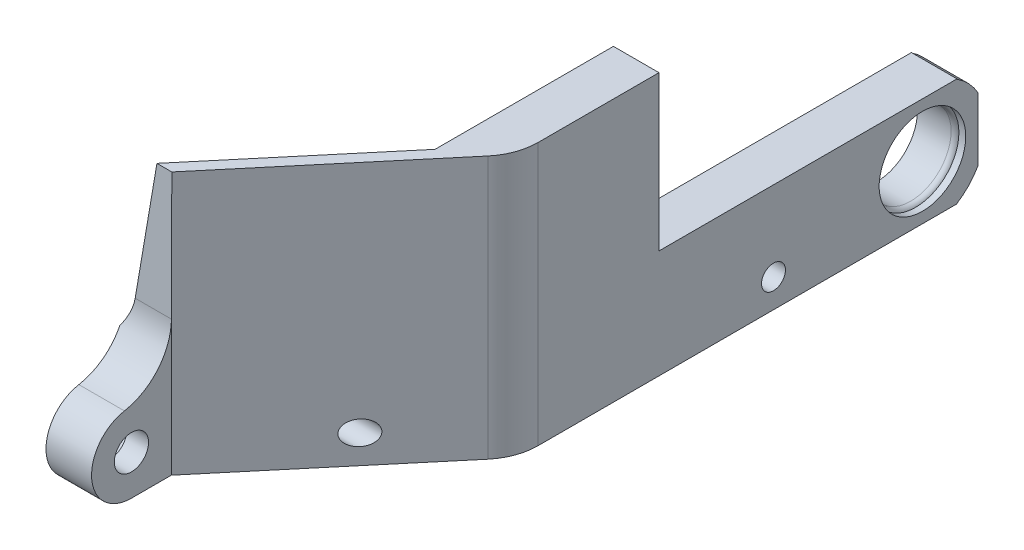
SolidWorks part; units mm, degrees
ref_plane "Front Plane" through (0, 0, 0) normal (0, 0, 1) x (1, 0, 0)
ref_plane "Top Plane" through (0, 0, 0) normal (0, 1, 0) x (1, 0, 0)
ref_plane "Right Plane" through (0, 0, 0) normal (1, 0, 0) x (0, 0, -1)
sketch "Sketch1" plane through (0, 0, 0) normal (0, 1, 0) x (1, 0, 0)
  line L0 (0, 0) -> (8, 0)
  line L1 (0, 0) -> (0, -52.2403)
  line L2 (8, 0) -> (8, -52.2403)
  line L4 (5.6604, -58.6682) -> (-19.7071, -88.9)
  line L5 (-2.3396, -58.6682) -> (-27.7071, -88.9)
  line L6 (-27.7071, -88.9) -> (-27.7071, -102.9)
  line L7 (-27.7071, -102.9) -> (-19.7071, -102.9)
  line L8 (-19.7071, -102.9) -> (-19.7071, -88.9)
  arc A0 (5.6604, -58.6682) -> (8, -52.2403) centre (-2, -52.2403) ccw
  arc A1 (-2.3396, -58.6682) -> (0, -52.2403) centre (-10, -52.2403) ccw
  point P8 (8, -55.88)
  point P16 (-19.7071, -88.9)
  dimension "D6" = 10
  dimension "D1" = 8
  dimension "D2" = 55.88
  dimension "D3" = 33.02
  dimension "D4" = 40
  dimension "D5" = 14
extrude "Boss-Extrude1" add sketch "Sketch1" along normal blind 46.1
sketch "Sketch2" plane through (-19.7071, 0, 0) normal (1, 0, 0) x (0, 0, -1)
  line L0 (-102.9, 0) -> (-88.9, 0) construction
  line L1 (-102.9, 46.1) -> (-102.9, 0) construction
  line L2 (-102.9, 46.1) -> (-102.9, 0)
  line L3 (-102.9, 46.1) -> (-88.8524, 46.1)
  line L4 (-102.9, 0) -> (-95.9, 0)
  line L6 (-95.9, 14) -> (-88.9, 14)
  line L7 (-88.9, 46.1) -> (-88.9, 0) construction
  line L8 (-88.9, 14) -> (-88.8524, 46.1)
  circle A0 centre (-95.9, 7) radius 5.1 construction
  arc A1 (-95.9, 14) -> (-95.9, 0) centre (-95.9, 7) ccw
  line M6 (-102.9, 0) -> (-88.9, 0)
  line M7 (-88.9, 0) -> (-88.9, 46.1)
  line M8 (-88.9, 46.1) -> (-102.9, 46.1)
  line M9 (-102.9, 46.1) -> (-102.9, 0)
  dimension "D1" = 7
  dimension "D3" = 10.2
  dimension "D2" = 7
extrude "Cut-Extrude1" cut sketch "Sketch2" against normal through all both and the other way through all contours A1 L6 M7 M8 M9 | A1 L2 M6 | L6 L8 L3 region at (-19.7071, 29.6473, 96.0243) region at (-19.7071, 1.5636, 101.3364) region at (-19.7071, 35.4, 88.8841)
sketch "Sketch3" plane through (-27.7071, 0, 0) normal (-1, 0, 0) x (0, 0, 1)
  circle A0 centre (95.9, 7) radius 5
  dimension "D1" = 10
extrude "Cut-Extrude2" cut sketch "Sketch3" against normal blind 4.2
sketch "Sketch4" plane through (-23.5071, 0, 0) normal (-1, 0, 0) x (0, 0, 1)
  circle A0 centre (95.9, 7) radius 3
  dimension "D1" = 6
extrude "Cut-Extrude3" cut sketch "Sketch4" against normal through all
sketch "Sketch5" plane through (0, 46.1, 0) normal (0, 1, 0) x (1, 0, 0)
  line L0 (-19.7071, -88.9) -> (-24.4017, -84.9608)
  line L1 (-2.3396, -58.6682) -> (-27.6671, -88.8524) construction
ref_plane "Plane1" through (-51.9172, 0, 61.8725) normal (-0.6428, 0, 0.766) x (0.766, 0, 0.6428)
sketch "Sketch7" plane through (-51.9172, 0, 61.8725) normal (-0.6428, 0, 0.766) x (0.766, 0, 0.6428)
  line L0 (42.0473, 14) -> (35.919, 14)
  line L1 (35.919, 14) -> (40.0473, 46.1)
  line L2 (42.0473, 46.1) -> (35.919, 46.1) construction
  line L3 (40.0473, 46.1) -> (42.0473, 46.1)
  line L4 (42.0473, 46.1) -> (42.0473, 14)
  line L5 (40.0473, 46.1) -> (20.8329, 46.1)
  line L6 (0, 46.1) -> (33.5794, 46.1) construction
  line L7 (20.8329, 46.1) -> (20.8329, 14)
  line L8 (20.8329, 14) -> (35.919, 14)
  dimension "D1" = 2
extrude "Cut-Extrude4" cut sketch "Sketch7" against normal up to surface and the other way through all contours L1 region at (-29.3576, 30.6939, 80.8022) up to face at (0, 23.05, 26.1201)
sketch "Sketch8" plane through (8, 0, 0) normal (1, 0, 0) x (0, 0, -1)
  line L0 (0, 46.1) -> (-31, 46.1)
  line L1 (-52.2403, 46.1) -> (0, 46.1) construction
  line L2 (-31, 46.1) -> (-31, 19)
  line L3 (-31, 19) -> (0, 19)
  line L4 (0, 46.1) -> (0, 0) construction
  line L5 (0, 19) -> (0, 46.1)
  line L6 (-52.2403, 0) -> (0, 0) construction
  dimension "D1" = 19
extrude "Cut-Extrude5" cut sketch "Sketch8" against normal through all
sketch "Sketch9" plane through (0, 0, 0) normal (0, 1, 0) x (1, 0, 0)
  line L0 (8, 0) -> (0, 0)
  line L1 (8, 0) -> (8, 25)
  line L2 (0, 0) -> (0, 25)
  line L3 (8, 25) -> (0, 25)
  dimension "D1" = 25
extrude "Boss-Extrude2" add sketch "Sketch9" along normal blind 19
sketch "Sketch10" plane through (8, 0, 0) normal (1, 0, 0) x (0, 0, -1)
  line L0 (25, 19) -> (25, 0) construction
  line L1 (-52.2403, 0) -> (25, 0) construction
  line L2 (21.2198, 0) -> (25, 0)
  line L5 (21.189, 19.0193) -> (21.3262, 19.0193)
  line L7 (21.2868, 18.9575) -> (21.3262, 19.0193) construction
  line L9 (-52.2403, 0) -> (25, 0) construction
  line L10 (25, 0) -> (25, 19)
  line L11 (25, 19) -> (21.3262, 19.0193)
  circle A0 centre (15.25, 9.5) radius 7.1
  arc A1 (21.2198, 0) -> (25, 3.9479) centre (15.25, 9.5) ccw
  arc A2 (25, 15.0521) -> (21.189, 19.0193) centre (15.25, 9.5) ccw
  line M7 (-52.2403, 0) -> (25, 0)
  line M8 (25, 0) -> (25, 19)
  line M9 (25, 19) -> (-31, 19)
  dimension "D1" = 14.2
  dimension "D4" = 11.22
  dimension "D2" = 9.75
  dimension "D3" = 9.5
extrude "Cut-Extrude6" cut sketch "Sketch10" against normal through all contours A1 M7 M8 | L7 A2 M8 M9 | A0 region at (8, 1.204, -23.8455) region at (8, 17.7956, -23.8463) region at (8, 9.5, -15.25)
sketch "Sketch11" plane through (8, 0, 0) normal (1, 0, 0) x (0, 0, -1)
  line L0 (-88.9, 14) -> (-88.9, 0) construction
  circle A0 centre (15.25, 9.5) radius 7.6
  dimension "D1" = 15.2
  dimension "D2" = 104.15
extrude "Cut-Extrude7" cut sketch "Sketch11" against normal blind 1.2
sketch "Sketch12" plane through (8, 0, 0) normal (1, 0, 0) x (0, 0, -1)
  line L0 (-88.9, 0) -> (-58.6682, 0) construction
  line L1 (-88.9, 14) -> (-88.9, 0) construction
  circle A0 centre (-70.9, 5) radius 2.1
  circle A1 centre (-10.9, 5) radius 2.1
  dimension "D1" = 5
  dimension "D2" = 4.2
  dimension "D3" = 18
  dimension "D4" = 60
extrude "Cut-Extrude8" cut sketch "Sketch12" against normal through all both and the other way through all
sketch "Sketch14" plane through (8, 0, 0) normal (1, 0, 0) x (0, 0, -1)
  circle A0 centre (-10.9, 5) radius 4
  circle A1 centre (-70.9, 5) radius 4
  circle M2 centre (-10.9, 5) radius 2.1
  dimension "D1" = 8
extrude "Cut-Extrude9" cut sketch "Sketch14" along normal blind 4.2 and the other way through all from surface contours A0 M2 region at (8, 5, 14.7869) starting at face at (0, 5, 8.8)
extrude "Cut-Extrude10" cut sketch "Sketch14<3>" along normal blind 4.2 from offset 24 contours A1 region at (8, 5, 70.9) offset against normal yes
sketch "Sketch14<3>" plane through (8, 0, 0) normal (1, 0, 0) x (0, 0, -1) same geometry as "Sketch14"
fillet "Fillet13" radius 10 1 edges at (-23.7071, 14, 88.9)
fillet "Fillet14" radius 1 1 edges at (6.8, 9.5, -22.35)
